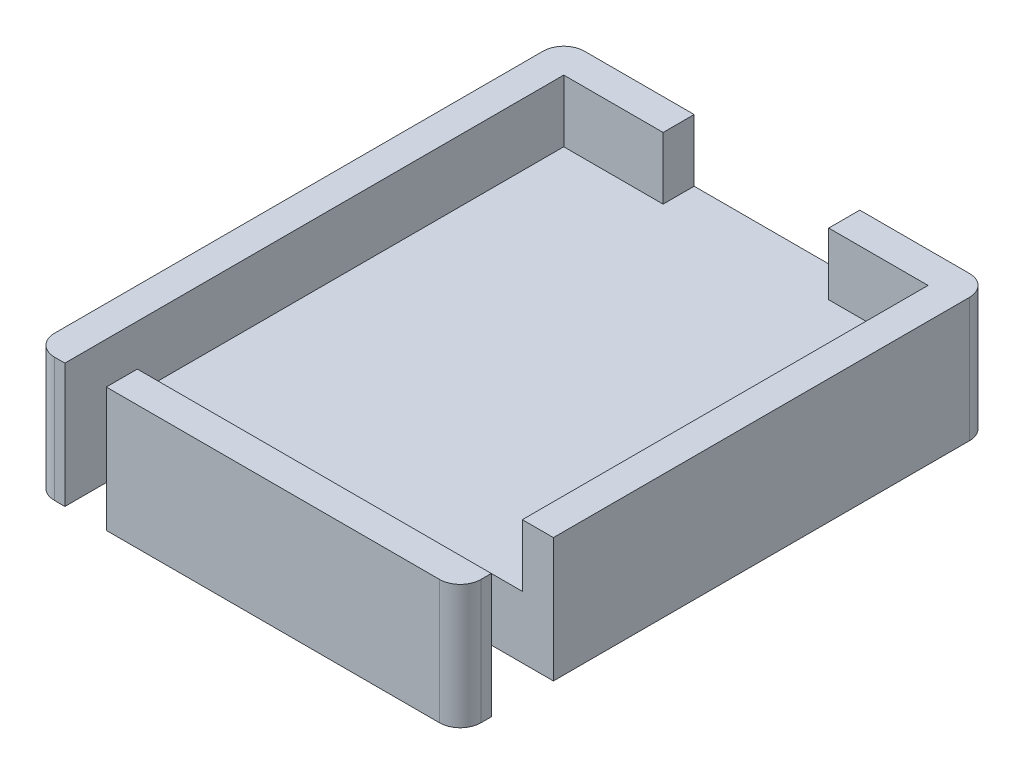
SolidWorks part; units mm, degrees
ref_plane "Alzado" through (0, 0, 0) normal (0, 0, 1) x (1, 0, 0)
ref_plane "Planta" through (0, 0, 0) normal (0, 1, 0) x (1, 0, 0)
ref_plane "Vista lateral" through (0, 0, 0) normal (1, 0, 0) x (0, 0, -1)
sketch "Croquis1" plane through (0, 0, 0) normal (0, 1, 0) x (1, 0, 0)
  line L0 (-9.3, 12.8) -> (9.3, 12.8)
  line L1 (-8.8, 11.3) -> (8.8, 11.3)
  line L2 (-8.8, 11.3) -> (-8.8, -11.3)
  line L3 (-8.8, -11.3) -> (8.8, -11.3)
  line L4 (8.8, 11.3) -> (8.8, -11.3)
  line L5 (-8.8, 11.3) -> (8.8, -11.3) construction
  line L6 (-8.8, -11.3) -> (8.8, 11.3) construction
  line L7 (10.3, 11.8) -> (10.3, -11.8)
  line L8 (-9.3, -12.8) -> (9.3, -12.8)
  line L9 (-10.3, 11.8) -> (-10.3, -11.8)
  line L10 (-10.3, -12.8) -> (10.3, -12.8) construction
  line L11 (-10.3, 12.8) -> (-10.3, -12.8) construction
  line L12 (10.3, 12.8) -> (10.3, -12.8) construction
  line L13 (-10.3, 12.8) -> (10.3, 12.8) construction
  line L14 (0, -1000) -> (0, 49000) construction
  line L15 (-4, 12.8) -> (4, 12.8)
  line L16 (-4, 12.8) -> (-4, 11.3)
  line L17 (-4, 11.3) -> (4, 11.3)
  line L18 (4, 12.8) -> (4, 11.3)
  line L19 (-4, 12.8) -> (4, 11.3) construction
  line L20 (-4, 11.3) -> (4, 12.8) construction
  arc A0 (-9.3, -12.8) -> (-10.3, -11.8) centre (-9.3, -11.8) cw
  arc A1 (10.3, -11.8) -> (9.3, -12.8) centre (9.3, -11.8) cw
  arc A2 (9.3, 12.8) -> (10.3, 11.8) centre (9.3, 11.8) cw
  arc A3 (-9.3, 12.8) -> (-10.3, 11.8) centre (-9.3, 11.8) ccw
  point P0 (0, 0)
  point P22 (0, 12.05)
  dimension "D4" = 1
  dimension "D1" = 17.6
  dimension "D2" = 22.6
  dimension "D5" = 8
  dimension "D3" = 1.5
extrude "Saliente-Extruir1" add sketch "Croquis1" along normal blind 3 contours L0 A3 L9 A0 L8 A1 L7 A2 L18 L1 L4 L3 L2 L16 region at (-6.65, 0, -12.4714)
extrude "Saliente-Extruir2" add sketch "Croquis1<3>" against normal blind 3 contours A2 L0 L18 L1 L4 L3 L8 A1 L7 | L18 L0 L16 L1 | L0 A3 L9 A0 L8 L3 L2 L1 L16 | L3 L8 | L3 L8 | L3 L8 | L3 L4 L1 L2 | L3 L4 region at (-6.65, 0, -12.4714) region at (0, 0, -12.05) region at (0, 0, 0)
sketch "Croquis1<3>" plane through (0, 0, 0) normal (0, 1, 0) x (1, 0, 0) same geometry as "Croquis1"
sketch "Croquis3" plane through (10.3, 0, 0) normal (1, 0, 0) x (0, 0, -1)
  line L0 (-11.3, 3) -> (-11.3, 0) construction
  line L1 (-11.3, 3) -> (-8.3, 3)
  line L2 (-11.3, 3) -> (-11.3, -3)
  line L3 (-11.3, -3) -> (-8.3, -3)
  line L4 (-8.3, 3) -> (-8.3, -3)
  line L5 (-11.3, 3) -> (-8.3, -3) construction
  line L6 (-11.3, -3) -> (-8.3, 3) construction
  line L7 (11.8, -3) -> (-11.8, -3) construction
  line L8 (11.8, 3) -> (-11.8, 3) construction
  point P0 (-9.8, 0)
  dimension "D1" = 3
extrude "Cortar-Extruir3" cut sketch "Croquis3" against normal blind 4
sketch "Croquis4" plane through (0, 0, 12.8) normal (0, 0, 1) x (1, 0, 0)
  line L0 (-8.8, 3) -> (-8.8, 0) construction
  line L1 (-8.8, 3) -> (-6.8, 3)
  line L2 (-8.8, 3) -> (-8.8, -3)
  line L3 (-8.8, -3) -> (-6.8, -3)
  line L4 (-6.8, 3) -> (-6.8, -3)
  line L5 (-8.8, 3) -> (-6.8, -3) construction
  line L6 (-8.8, -3) -> (-6.8, 3) construction
  line L7 (-9.3, -3) -> (9.3, -3) construction
  line L8 (-9.3, 3) -> (9.3, 3) construction
  point P0 (-7.8, 0)
  dimension "D1" = 2
extrude "Cortar-Extruir4" cut sketch "Croquis4" against normal blind 4
